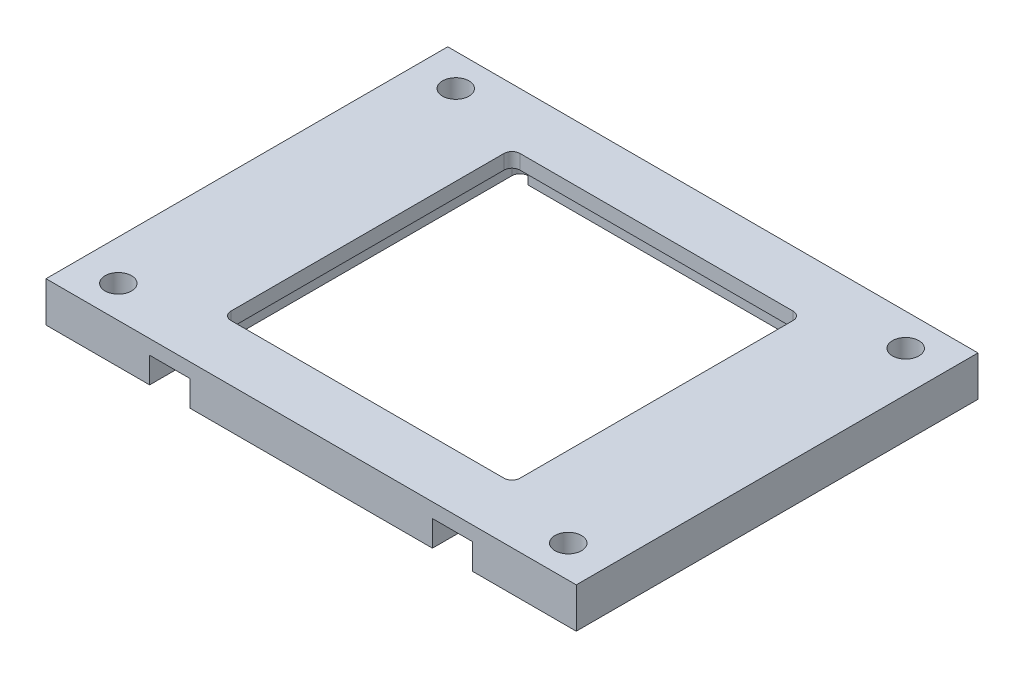
SolidWorks part; units mm, degrees
ref_plane "Front Plane" through (0, 0, 0) normal (0, 0, 1) x (1, 0, 0)
ref_plane "Top Plane" through (0, 0, 0) normal (0, 1, 0) x (1, 0, 0)
ref_plane "Right Plane" through (0, 0, 0) normal (1, 0, 0) x (0, 0, -1)
sketch "Sketch1" plane through (0, 0, 0) normal (0, 1, 0) x (1, 0, 0)
  line L0 (20.1, -20.1) -> (20.1, 21.1)
  line L1 (-20.1, -20.1) -> (20.1, -20.1)
  line L3 (-18.1, 20.1) -> (18.1, 20.1)
  line L5 (-20.1, 21.1) -> (-20.1, -20.1)
  line L7 (-33, -25) -> (33, -25)
  line L8 (-33, -25) -> (-33, 25)
  line L9 (-33, 25) -> (33, 25)
  line L10 (33, -25) -> (33, 25)
  line L11 (-33, -25) -> (33, 25) construction
  line L12 (-33, 25) -> (33, -25) construction
  line L15 (-20.1, 21.1) -> (-18.1, 21.1)
  line L16 (-18.1, 20.1) -> (-18.1, 21.1)
  line L19 (20.1, 21.1) -> (18.1, 21.1)
  line L20 (18.1, 20.1) -> (18.1, 21.1)
  circle A0 centre (-28, 21) radius 1.65
  circle A1 centre (28, 21) radius 1.65
  circle A2 centre (-28, -21) radius 1.65
  circle A3 centre (28, -21) radius 1.65
  point P0 (0, 0)
  point P1 (-29.5684, 26.4118)
  point P3 (0, 0)
  point P15 (0, 0)
  dimension "D3" = 21
  dimension "D4" = 21
  dimension "D5" = 21
  dimension "D6" = 21
  dimension "D7" = 28
  dimension "D10" = 28
  dimension "D11" = 3.3
  dimension "D14" = 2
  dimension "D2" = 40.2
  dimension "D8" = 28
  dimension "D9" = 28
  dimension "D12" = 66
  dimension "D13" = 50
  dimension "D15" = 1
  dimension "D16" = 2
  dimension "D17" = 1
  dimension "D18" = 20.1
  dimension "D19" = 40.2
  dimension "D20" = 20.1
extrude "Boss-Extrude1" add sketch "Sketch1" along normal blind 5
sketch "Sketch2" plane through (0, 5, 0) normal (0, 1, 0) x (1, 0, 0)
  line L12 (-18, -18) -> (18, -18)
  line L13 (18, -18) -> (18, 18)
  line L14 (-18, 18) -> (-18, -18)
  line L15 (18, 18) -> (-18, 18)
  line L54 (-20.1, 21.1) -> (-20.1, -20.1)
  line L55 (-20.1, -20.1) -> (20.1, -20.1)
  line L56 (20.1, -20.1) -> (20.1, 21.1)
  line L57 (20.1, 21.1) -> (18.1, 21.1)
  line L58 (18.1, 21.1) -> (18.1, 20.1)
  line L59 (18.1, 20.1) -> (-18.1, 20.1)
  line L60 (-18.1, 20.1) -> (-18.1, 21.1)
  line L61 (-18.1, 21.1) -> (-20.1, 21.1)
  line L62 (-20.1, 21.1) -> (-20.1, -20.1)
  line L63 (-20.1, -20.1) -> (20.1, -20.1)
  line L64 (20.1, -20.1) -> (20.1, 21.1)
  line L65 (20.1, 21.1) -> (18.1, 21.1)
  line L66 (18.1, 21.1) -> (18.1, 20.1)
  line L67 (18.1, 20.1) -> (-18.1, 20.1)
  line L68 (-18.1, 20.1) -> (-18.1, 21.1)
  line L69 (-18.1, 21.1) -> (-20.1, 21.1)
  dimension "D1" = 36
  dimension "D3" = 36
  dimension "D4" = 18
  dimension "D5" = 18
  dimension "D6" = 36
  dimension "D7" = 36
  dimension "D2" = 0
extrude "Boss-Extrude2" add sketch "Sketch2" against normal blind 1.8
sketch "Sketch3" plane through (0, 0, 25) normal (0, 0, 1) x (1, 0, 0)
  line L0 (-33, 0) -> (33, 0) construction
  line L1 (-20.1, 0) -> (-15.1, 0)
  line L3 (-20.1, 3.2) -> (-15.1, 3.2)
  line L4 (-15.1, 0) -> (-15.1, 3.2)
  line L5 (20.1, 0) -> (20.1, 3.2)
  line L6 (20.1, 0) -> (15.1, 0)
  line L8 (20.1, 3.2) -> (15.1, 3.2)
  line L9 (15.1, 0) -> (15.1, 3.2)
  line L10 (-20.1, 0) -> (-20.1, 3.2)
  dimension "D1" = 5
  dimension "D2" = 5
  dimension "D3" = 0
  dimension "D4" = 0
  dimension "D5" = 3.2
  dimension "D6" = 3.2
extrude "Cut-Extrude1" cut sketch "Sketch3" against normal up to next
fillet "Fillet1" radius 1 8 edges at (-18, 4.1, 18) (18, 4.1, 18) (18, 4.1, -18) (-18, 4.1, -18) (-20.1, 1.6, -21.1) (-18.1, 1.6, -21.1) (18.1, 1.6, -21.1) (20.1, 1.6, -21.1)
